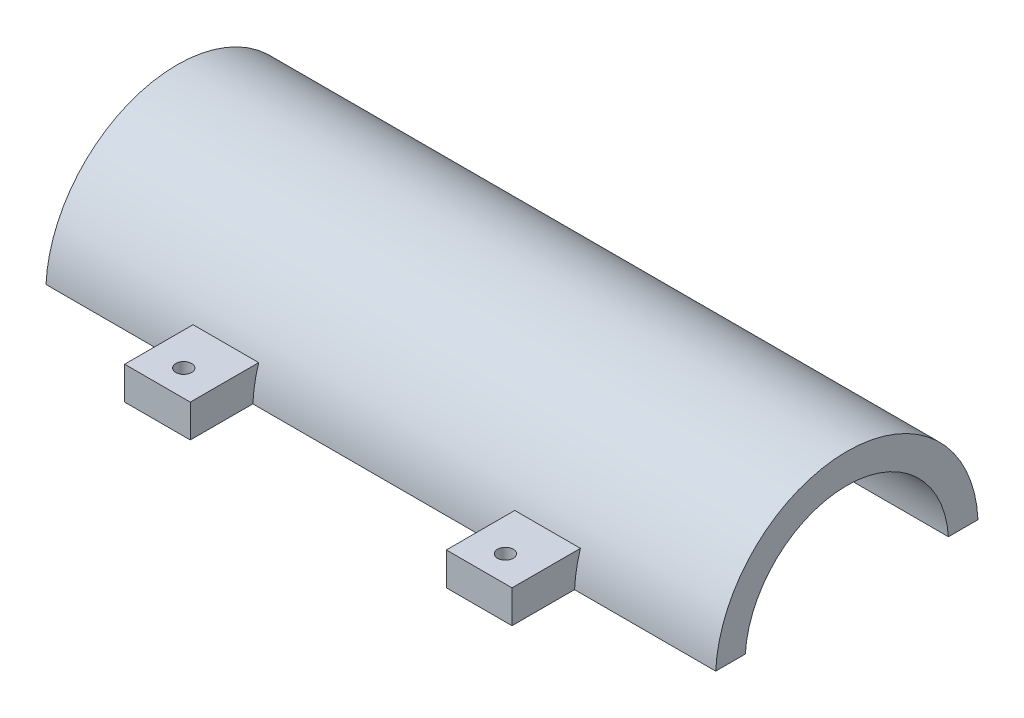
SolidWorks part; units mm, degrees
ref_plane "Front Plane" through (0, 0, 0) normal (0, 0, 1) x (1, 0, 0)
ref_plane "Top Plane" through (0, 0, 0) normal (0, 1, 0) x (1, 0, 0)
ref_plane "Right Plane" through (0, 0, 0) normal (1, 0, 0) x (0, 0, -1)
sketch "Sketch1" plane through (0, 0, 0) normal (1, 0, 0) x (0, 0, -1)
  line L1 (-20.9452, 21.1459) -> (13.0548, 21.1459)
  line L2 (-20.9452, 21.1459) -> (-20.9452, -8.8541)
  line L3 (-20.9452, -8.8541) -> (13.0548, -8.8541)
  line L4 (13.0548, 21.1459) -> (13.0548, -8.8541)
  dimension "D1" = 34
  dimension "D2" = 30
extrude "Boss-Extrude2" add sketch "Sketch1" along normal blind 51
sketch "Sketch3" plane through (0, 0, -13.0548) normal (0, 0, -1) x (-1, 0, 0)
  line L0 (-51, -8.8541) -> (0, -8.8541) construction
  line L1 (-51, -8.8541) -> (-51, 21.1459) construction
  circle A0 centre (-25.5, -1.3541) radius 2.55
  point P2 (-25.5, -8.8541)
  dimension "D1" = 7.5
  dimension "D2" = 5.1
  dimension "D3" = 25.5
extrude "Cut-Extrude3" cut sketch "Sketch3" against normal blind 10
sketch "Sketch5" plane through (51, 0, 0) normal (1, 0, 0) x (0, 0, -1)
  line L0 (13.0548, -8.8541) -> (13.0548, 21.1459) construction
  line L1 (-20.9452, -8.8541) -> (13.0548, -8.8541) construction
  circle A0 centre (-3.9452, 1.1459) radius 7.75
  dimension "D1" = 17
  dimension "D2" = 10
extrude "Cut-Extrude4" cut sketch "Sketch5" against normal blind 51
sketch "Sketch6" plane through (51, 0, 0) normal (1, 0, 0) x (0, 0, -1)
  line L0 (-20.9452, -8.8541) -> (13.0548, -8.8541) construction
  line L1 (13.0548, 21.1459) -> (6.0548, 21.1459)
  line L2 (13.0548, 21.1459) -> (13.0548, -8.8541)
  line L3 (13.0548, -8.8541) -> (6.0548, -8.8541)
  line L4 (6.0548, 21.1459) -> (6.0548, -8.8541)
  dimension "D1" = 7
extrude "Cut-Extrude6" cut sketch "Sketch6" against normal blind 51
sketch "Sketch7" plane through (51, 0, 0) normal (1, 0, 0) x (0, 0, -1)
  line L1 (-3.9452, -8.8541) -> (-20.9452, -8.8541)
  line L2 (6.0548, 1.1459) -> (6.0548, 21.1459)
  line L3 (6.0548, 21.1459) -> (-20.9452, 21.1459)
  line L4 (-20.9452, -8.8541) -> (-20.9452, 21.1459)
  arc A0 (6.0548, 1.1459) -> (-3.9452, -8.8541) centre (-3.9452, 1.1459) ccw
extrude "Cut-Extrude7" cut sketch "Sketch7" against normal blind 51
sketch "Sketch8" plane through (0, 0, -3.0548) normal (0, 0, -1) x (-1, 0, 0)
  line L2 (-21.75, -2.1801) -> (-21.75, -4.9041)
  line L3 (-21.75, -4.9041) -> (-29.25, -4.9041)
  line L4 (-29.25, -2.1801) -> (-29.25, -4.9041)
  line L6 (-29.25, -2.1801) -> (-29.25, 2.1959)
  line L7 (-29.25, 2.1959) -> (-21.75, 2.1959)
  line L8 (-21.75, -2.1801) -> (-21.75, 2.1959)
  arc A0 (-27.9125, -2.1801) -> (-23.0875, -2.1801) centre (-25.5, -1.3541) ccw construction
  arc A1 (-24.9975, 1.1459) -> (-26.0025, 1.1459) centre (-25.5, -1.3541) ccw construction
  point P4 (-25.5, -3.9041)
  point P8 (-25.5, -3.9041)
  point P11 (-25.5, 1.1959)
  dimension "D1" = 7.5
  dimension "D2" = 3.75
  dimension "D3" = 1
  dimension "D4" = 1
extrude "Cut-Extrude9" cut sketch "Sketch8" against normal blind 1.5 and the other way blind 1.5
sketch "Sketch10" plane through (51, 0, 0) normal (1, 0, 0) x (0, 0, -1)
  line L1 (-17.6952, 1.1459) -> (-17.6952, 4.1459)
  line L2 (-17.6952, 4.1459) -> (-11.6952, 4.1459)
  line L3 (-11.6952, 4.1459) -> (-11.6952, 1.1459)
  line L4 (-11.6952, -1.8541) -> (-17.6952, -1.8541)
  line L5 (-17.6952, -1.8541) -> (-17.6952, 1.1459)
  line L6 (-11.6952, -1.8541) -> (-11.6952, 1.1459)
  circle A0 centre (-3.9452, 1.1459) radius 7.75 construction
  dimension "D1" = 3
  dimension "D2" = 3
  dimension "D3" = 6
extrude "Boss-Extrude5" add sketch "Sketch10" against normal blind 51
sketch "Sketch11" plane through (51, 0, 0) normal (1, 0, 0) x (0, 0, -1)
  line L0 (-13.4846, -1.8541) -> (-17.6952, -1.8541)
  line L1 (-17.6952, -1.8541) -> (-17.6952, 4.1459)
  line L2 (-17.6952, 4.1459) -> (-13.4846, 4.1459)
  arc A0 (-13.4846, 4.1459) -> (-13.4846, -1.8541) centre (-3.9452, 1.1459) ccw
extrude "Cut-Extrude10" cut sketch "Sketch11" against normal blind 13
sketch "Sketch12" plane through (0, 0, 0) normal (-1, 0, 0) x (0, 0, 1)
  line L0 (13.4846, -1.8541) -> (17.6952, -1.8541)
  line L1 (17.6952, -1.8541) -> (17.6952, 4.1459)
  line L2 (17.6952, 4.1459) -> (13.4846, 4.1459)
  arc A0 (13.4846, -1.8541) -> (13.4846, 4.1459) centre (3.9452, 1.1459) ccw
extrude "Cut-Extrude11" cut sketch "Sketch12" against normal blind 13
sketch "Sketch13" plane through (0, 0, 17.6952) normal (0, 0, 1) x (1, 0, 0)
  line L0 (13, -1.8541) -> (13, 4.1459) construction
  line L1 (24.5, -1.8541) -> (26.5, -1.8541)
  line L2 (24.5, -1.8541) -> (24.5, 4.1459)
  line L3 (24.5, 4.1459) -> (26.5, 4.1459)
  line L4 (26.5, -1.8541) -> (26.5, 4.1459)
  line L5 (38, 4.1459) -> (38, -1.8541) construction
  line L6 (13, 4.1459) -> (38, 4.1459) construction
  line L7 (13, -1.8541) -> (38, -1.8541) construction
  dimension "D1" = 2
  dimension "D2" = 11.5
  dimension "D3" = 11.5
  dimension "D4" = 0
  dimension "D5" = 0
extrude "Cut-Extrude12" cut sketch "Sketch13" against normal blind 2
sketch "Sketch15" plane through (24.5, 0, 0) normal (1, 0, 0) x (0, 0, -1)
  line L0 (-17.6952, 4.1459) -> (-17.6952, -1.8541)
  line L1 (-17.6952, -1.8541) -> (-13.4846, -1.8541)
  line L2 (-13.4846, -1.8541) -> (-17.6952, -1.8541) construction
  line L4 (-13.4846, 4.1459) -> (-17.6952, 4.1459)
  arc A0 (-13.4846, 4.1459) -> (-13.4846, -1.8541) centre (-3.9452, 1.1459) ccw
extrude "Cut-Extrude13" cut sketch "Sketch15" against normal blind 11 and the other way blind 13
sketch "Sketch17" plane through (38, 0, 0) normal (1, 0, 0) x (0, 0, -1)
  line L0 (-13.4846, 4.1459) -> (-17.6952, 4.1459)
  line L1 (-17.6952, 4.1459) -> (-17.6952, -1.8541)
  line L2 (-17.6952, -1.8541) -> (-13.4846, -1.8541)
  arc A0 (-13.4846, 4.1459) -> (-13.4846, -1.8541) centre (-3.9452, 1.1459) ccw
extrude "Boss-Extrude6" add sketch "Sketch17" along normal blind 2.25
sketch "Sketch19" plane through (13, 0, 0) normal (-1, 0, 0) x (0, 0, 1)
  line L0 (13.4846, 4.1459) -> (17.6952, 4.1459)
  line L1 (17.6952, 4.1459) -> (17.6952, -1.8541)
  line L2 (17.6952, -1.8541) -> (13.4846, -1.8541)
  arc A0 (13.4846, -1.8541) -> (13.4846, 4.1459) centre (3.9452, 1.1459) ccw
extrude "Boss-Extrude7" add sketch "Sketch19" along normal blind 2.25
sketch "Sketch20" plane through (13.5, 0, 0) normal (1, 0, 0) x (0, 0, -1)
  line L0 (-17.6952, -1.8541) -> (-17.6952, 4.1459)
  line L1 (-17.6952, 4.1459) -> (-13.4846, 4.1459)
  line L3 (-13.4846, -1.8541) -> (-17.6952, -1.8541)
  arc A0 (-13.4846, 4.1459) -> (-13.4846, -1.8541) centre (-3.9452, 1.1459) ccw
extrude "Boss-Extrude8" add sketch "Sketch20" along normal blind 2.25
sketch "Sketch21" plane through (37.5, 0, 0) normal (-1, 0, 0) x (0, 0, 1)
  line L0 (13.4846, 4.1459) -> (17.6952, 4.1459)
  line L1 (17.6952, 4.1459) -> (17.6952, -1.8541)
  line L2 (17.6952, -1.8541) -> (13.4846, -1.8541)
  line L3 (13.4846, -1.8541) -> (17.6952, -1.8541) construction
  arc A0 (13.4846, -1.8541) -> (13.4846, 4.1459) centre (3.9452, 1.1459) ccw
extrude "Boss-Extrude9" add sketch "Sketch21" along normal blind 2.25
sketch "Sketch22" plane through (0, 0, 17.6952) normal (0, 0, 1) x (1, 0, 0)
  line L1 (35.25, -1.8541) -> (40.25, -1.8541)
  line L2 (35.25, -1.8541) -> (35.25, 4.1459)
  line L3 (35.25, 4.1459) -> (40.25, 4.1459)
  line L4 (40.25, -1.8541) -> (40.25, 4.1459)
extrude "Boss-Extrude10" add sketch "Sketch22" along normal blind 1
sketch "Sketch24" plane through (0, 0, 17.6952) normal (0, 0, 1) x (1, 0, 0)
  line L1 (10.75, -1.8541) -> (15.75, -1.8541)
  line L2 (10.75, -1.8541) -> (10.75, 4.1459)
  line L3 (10.75, 4.1459) -> (15.75, 4.1459)
  line L4 (15.75, -1.8541) -> (15.75, 4.1459)
extrude "Boss-Extrude11" add sketch "Sketch24" along normal blind 1
sketch "Sketch25" plane through (0, 4.1459, 0) normal (0, 1, 0) x (1, 0, 0)
  line L0 (10.75, -18.6952) -> (10.75, -13.4846) construction
  line L1 (15.75, -13.4846) -> (15.75, -18.6952) construction
  line L2 (15.75, -18.6952) -> (10.75, -18.6952) construction
  line L3 (10.75, -13.4846) -> (15.75, -13.4846) construction
  line L4 (40.25, -13.4846) -> (40.25, -18.6952) construction
  circle A0 centre (13.25, -16.6952) radius 0.6
  circle A1 centre (37.75, -16.6952) radius 0.6
  dimension "D1" = 2.5
  dimension "D5" = 2.5
  dimension "D2" = 2.5
  dimension "D3" = 2
  dimension "D4" = 3.2106
extrude "Cut-Extrude14" cut sketch "Sketch25" against normal blind 20
sketch "Sketch26" plane through (0, 0, -6.0548) normal (0, 0, -1) x (-1, 0, 0)
  circle A0 centre (-25.5, -1.3541) radius 2.55
  dimension "D1" = 5.1
extrude "Boss-Extrude12" add sketch "Sketch26" against normal blind 1.5
sketch "Sketch27" plane through (51, 0, 0) normal (1, 0, 0) x (0, 0, -1)
  line L1 (-18.6952, -1.8541) -> (-18.6952, 4.1459) construction
  line L3 (-18.6952, 1.1459) -> (-18.6952, 1.6459)
  line L4 (-18.6952, 1.6459) -> (6.5948, 1.6459)
  line L5 (6.5948, 1.1459) -> (6.5948, 1.6459)
  line L8 (-18.6952, 1.1459) -> (-18.6952, 0.6459)
  line L10 (6.5948, 1.1459) -> (6.5948, 0.6459)
  line L12 (-18.6952, 0.6459) -> (-18.6952, -9.8456)
  line L13 (-18.6952, -9.8456) -> (6.5948, -9.8456)
  line L14 (6.5948, 0.6459) -> (6.5948, -9.8456)
  dimension "D1" = 0.5
  dimension "D2" = 0.5
extrude "Cut-Extrude17" cut sketch "Sketch27" against normal blind 60
